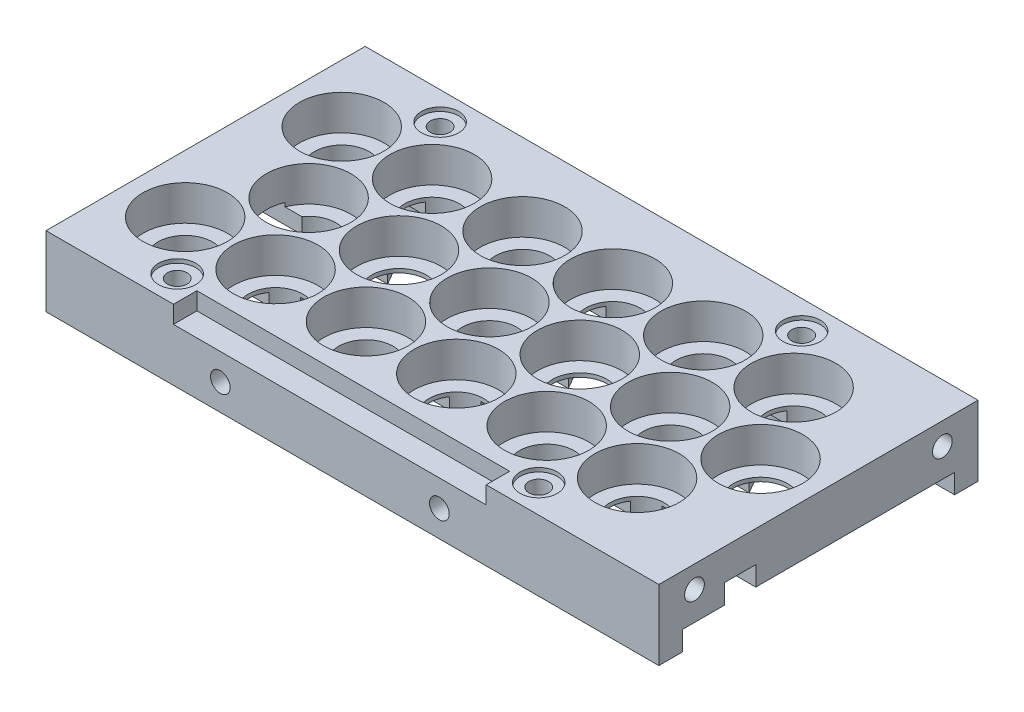
SolidWorks part; units mm, degrees
ref_plane "Front Plane" through (0, 0, 0) normal (0, 0, 1) x (1, 0, 0)
ref_plane "Top Plane" through (0, 0, 0) normal (0, 1, 0) x (1, 0, 0)
ref_plane "Right Plane" through (0, 0, 0) normal (1, 0, 0) x (0, 0, -1)
sketch "Sketch1" plane through (0, 0, 0) normal (0, 1, 0) x (1, 0, 0)
  line L0 (0, 0) -> (11.575, -20.0485) construction
  line L1 (11.575, -20.0485) -> (0, -40.097) construction
  line L2 (0, 0) -> (11.575, 0) construction
  line L3 (11.575, 0) -> (11.575, -20.0485) construction
  line L4 (11.575, -20.0485) -> (11.575, -40.097) construction
  line L5 (11.575, -40.097) -> (0, -40.097) construction
  line L6 (0, 0) -> (23.15, 0) construction
  line L7 (0, 0) -> (23.15, 0) construction
  line L8 (-14.825, -60.922) -> (142.15, -60.922)
  line L9 (-14.825, -60.922) -> (-14.825, 20.825)
  line L10 (-14.825, 20.825) -> (142.15, 20.825)
  line L11 (142.15, -60.922) -> (142.15, 20.825)
  circle A0 centre (0, 0) radius 10.825
  circle A1 centre (11.575, -20.0485) radius 10.825
  circle A2 centre (0, -40.097) radius 10.825
  circle A3 centre (23.15, 0) radius 10.825
  circle A4 centre (34.725, -20.0485) radius 10.825
  circle A5 centre (23.15, -40.097) radius 10.825
  circle A6 centre (46.3, 0) radius 10.825
  circle A7 centre (57.875, -20.0485) radius 10.825
  circle A8 centre (46.3, -40.097) radius 10.825
  circle A9 centre (69.45, 0) radius 10.825
  circle A10 centre (81.025, -20.0485) radius 10.825
  circle A11 centre (69.45, -40.097) radius 10.825
  circle A12 centre (92.6, 0) radius 10.825
  circle A13 centre (104.175, -20.0485) radius 10.825
  circle A14 centre (92.6, -40.097) radius 10.825
  circle A15 centre (115.75, 0) radius 10.825
  circle A16 centre (127.325, -20.0485) radius 10.825
  circle A17 centre (115.75, -40.097) radius 10.825
  circle A18 centre (0, 0) radius 7
  circle A19 centre (11.575, -20.0485) radius 7
  circle A20 centre (0, -40.097) radius 7
  circle A21 centre (23.15, 0) radius 7
  circle A22 centre (34.725, -20.0485) radius 7
  circle A23 centre (23.15, -40.097) radius 7
  circle A24 centre (46.3, 0) radius 7
  circle A25 centre (57.875, -20.0485) radius 7
  circle A26 centre (46.3, -40.097) radius 7
  circle A27 centre (69.45, 0) radius 7
  circle A28 centre (81.025, -20.0485) radius 7
  circle A29 centre (69.45, -40.097) radius 7
  circle A30 centre (92.6, 0) radius 7
  circle A31 centre (104.175, -20.0485) radius 7
  circle A32 centre (92.6, -40.097) radius 7
  circle A33 centre (115.75, 0) radius 7
  circle A34 centre (127.325, -20.0485) radius 7
  circle A35 centre (115.75, -40.097) radius 7
  dimension "D3" = 21.65
  dimension "D11" = 14
  dimension "D1" = 60
  dimension "D2" = 60
  dimension "D4" = 1.5
  dimension "D6" = 23.15
  dimension "D7" = 4
  dimension "D8" = 4
  dimension "D9" = 10
  dimension "D10" = 10
  dimension "D13" = 23.15
  dimension "D5" = 6
  dimension "D12" = 6
extrude "Boss-Extrude2" add sketch "Sketch1" along normal blind 11 and the other way blind 2 contours L8 L11 L10 L9 A17 A16 A15 A14 A13 A12 A11 A10 A9 A8 A7 A6 A5 A4 A3 A2 A1 A0 region at (-13.0551, 0, 20.0485)
extrude "Boss-Extrude3" add sketch "Sketch1<3>" along normal blind 2 and the other way blind 2 contours A0 A18 | A3 A21 | A6 A24 | A9 A27 | A12 A30 | A15 A33 | A1 A19 | A4 A22 | A7 A25 | A10 A28 | A13 A31 | A16 A34 | A17 A35 | A14 A32 | A11 A29 | A8 A26 | A5 A23 | A2 A20 region at (-10.5188, 0, 0) region at (1.0562, 0, 20.0485) region at (-10.5188, 0, 40.097) region at (12.6312, 0, 0) region at (24.2062, 0, 20.0485) region at (12.6312, 0, 40.097) region at (35.7812, 0, 0) region at (47.3562, 0, 20.0485) region at (35.7812, 0, 40.097) region at (58.9312, 0, 0) region at (70.5062, 0, 20.0485) region at (58.9312, 0, 40.097) region at (82.0812, 0, 0) region at (93.6562, 0, 20.0485) region at (82.0812, 0, 40.097) region at (105.2312, 0, 0) region at (116.8062, 0, 20.0485) region at (105.2312, 0, 40.097)
sketch "Sketch1<3>" plane through (0, 0, 0) normal (0, 1, 0) x (1, 0, 0) same geometry as "Sketch1"
sketch "Sketch9" plane through (0, 11, 0) normal (0, 1, 0) x (1, 0, 0)
  line L0 (11.575, -60.922) -> (11.575, 20.825)
  line L1 (-14.825, 20.825) -> (142.15, 20.825) construction
  line L2 (104.175, 20.825) -> (104.175, -60.922)
  line L3 (-14.825, -60.922) -> (142.15, -60.922) construction
  circle A0 centre (11.575, 13.625) radius 2.525
  circle A1 centre (11.575, -53.722) radius 2.525
  circle A2 centre (104.175, -53.722) radius 2.525
  circle A3 centre (104.175, 13.625) radius 2.525
  point P0 (11.575, 13.625)
  point P7 (11.575, -20.0485)
  point P15 (104.175, -20.0485)
  point P20 (104.175, 13.625)
  point P21 (104.175, -53.722)
  point P22 (11.575, -53.722)
  dimension "D5" = 5.05
  dimension "D1" = 7.2
  dimension "D4" = 7.2
extrude "Cut-Extrude3" cut sketch "Sketch9" against normal up to next contours A2 | A1 | A0 | A3
sketch "Sketch10" plane through (0, 11, 0) normal (0, 1, 0) x (1, 0, 0)
  circle A0 centre (11.575, 13.625) radius 4.7625
  circle A1 centre (104.175, 13.625) radius 4.7625
  circle A2 centre (104.175, -53.722) radius 4.7625
  circle A3 centre (11.575, -53.722) radius 4.7625
  dimension "D1" = 9.525
extrude "Cut-Extrude4" cut sketch "Sketch10" against normal blind 1
sketch "Sketch13" plane through (0, -2, 0) normal (0, -1, 0) x (1, 0, 0)
  line L0 (142.15, 60.922) -> (142.15, -20.825) construction
  line L5 (3.575, 53.722) -> (3.575, 60.922)
  line L8 (-14.825, 60.922) -> (142.15, 60.922) construction
  line L9 (3.575, 60.922) -> (19.575, 60.922)
  line L10 (19.575, 60.922) -> (19.575, 53.722)
  line L12 (57.875, 20.0485) -> (57.875, -20.825) construction
  line L13 (-14.825, -20.825) -> (142.15, -20.825) construction
  line L14 (11.575, 20.0485) -> (127.325, 20.0485) construction
  line L16 (96.175, 60.922) -> (96.175, 53.722)
  line L17 (112.175, 60.922) -> (96.175, 60.922)
  line L18 (112.175, 53.722) -> (112.175, 60.922)
  line L19 (-14.825, 60.922) -> (142.15, 60.922)
  line L20 (-14.825, 60.922) -> (-14.825, 54.922)
  line L21 (-14.825, 54.922) -> (142.15, 54.922)
  line L22 (142.15, 60.922) -> (142.15, 54.922)
  line L23 (142.15, -20.825) -> (142.15, -14.825)
  line L24 (-14.825, -14.825) -> (142.15, -14.825)
  line L25 (-14.825, -20.825) -> (-14.825, -14.825)
  line L26 (-14.825, -20.825) -> (142.15, -20.825)
  line L27 (112.175, -13.625) -> (112.175, -20.825)
  line L28 (112.175, -20.825) -> (96.175, -20.825)
  line L29 (96.175, -20.825) -> (96.175, -13.625)
  line L32 (19.575, -20.825) -> (19.575, -13.625)
  line L33 (3.575, -20.825) -> (19.575, -20.825)
  line L34 (3.575, -13.625) -> (3.575, -20.825)
  circle A4 centre (11.575, 53.722) radius 6.5
  circle A5 centre (11.575, 53.722) radius 8
  circle A6 centre (104.175, 53.722) radius 8
  circle A7 centre (104.175, 53.722) radius 6.5
  circle A8 centre (104.175, -13.625) radius 6.5
  circle A9 centre (104.175, -13.625) radius 8
  circle A10 centre (11.575, -13.625) radius 8
  circle A11 centre (11.575, -13.625) radius 6.5
  line M15 (142.15, 60.922) -> (-14.825, 60.922)
  line M16 (-14.825, 60.922) -> (-14.825, -20.825)
  line M17 (-14.825, -20.825) -> (142.15, -20.825)
  line M18 (142.15, -20.825) -> (142.15, 60.922)
  dimension "D1" = 13
  dimension "D2" = 16
  dimension "D3" = 6
extrude "Boss-Extrude7" add sketch "Sketch13" along normal blind 5 contours L21 L5 M16 M15 | A5 L5 L21 M15 | A5 L21 L10 M15 | L10 L21 L16 M15 | L21 A5 L19 A4 | A5 L21 A4 | L21 A6 L16 M15 | L21 A7 A6 L19 | L21 A7 A6 | A6 L21 L18 M15 | L18 L21 M18 M15 | A9 L24 L29 L26 | L28 A9 L24 A8 | A9 L26 L27 L24 | L24 L27 L26 M18 | L32 L26 L29 L24 | L24 A9 A8 | L34 L24 M16 M17 | L26 A10 L24 L34 | L24 A11 A10 | L24 A11 A10 L33 | L24 A10 L26 L32 region at (3.7817, -2, 54.3098) region at (-5.625, -2, 57.922) region at (4.8282, -2, 59.2567) region at (5.2714, -2, 58.3681) region at (18.3218, -2, 59.2567) region at (57.875, -2, 57.922) region at (-5.625, -2, -17.825) region at (97.4282, -2, 59.2567) region at (4.8282, -2, -19.1597) region at (96.3817, -2, 54.3098) region at (97.8714, -2, 58.3681) region at (3.7817, -2, -14.2128) region at (4.4261, -2, -14.9942) region at (110.9218, -2, 59.2567) region at (127.1625, -2, 57.922) region at (18.3218, -2, -19.1597) region at (57.875, -2, -17.825) region at (97.4282, -2, -19.1597) region at (127.1625, -2, -17.825) region at (96.3817, -2, -14.2128) region at (97.0261, -2, -14.9942) region at (110.9218, -2, -19.1597)
sketch "Sketch2" plane through (0, -2, 0) normal (0, -1, 0) x (1, 0, 0)
  line L0 (0, 40.097) -> (11.575, 20.0485) construction
  line L1 (3.4641, 42.097) -> (15.0391, 22.0485)
  line L2 (-3.4641, 38.097) -> (8.1109, 18.0485)
  line L3 (11.575, 20.0485) -> (0, 0) construction
  line L4 (15.0391, 18.0485) -> (3.4641, -2)
  line L5 (8.1109, 22.0485) -> (-3.4641, 2)
  line L6 (19.6859, 38.097) -> (31.2609, 18.0485)
  line L7 (26.6141, 42.097) -> (38.1891, 22.0485)
  line L8 (31.2609, 22.0485) -> (19.6859, 2)
  line L9 (38.1891, 18.0485) -> (26.6141, -2)
  line L10 (23.15, 40.097) -> (34.725, 20.0485) construction
  line L11 (34.725, 20.0485) -> (23.15, 0) construction
  line L12 (42.8359, 38.097) -> (54.4109, 18.0485)
  line L13 (49.7641, 42.097) -> (61.3391, 22.0485)
  line L14 (54.4109, 22.0485) -> (42.8359, 2)
  line L15 (61.3391, 18.0485) -> (49.7641, -2)
  line L16 (46.3, 40.097) -> (57.875, 20.0485) construction
  line L17 (57.875, 20.0485) -> (46.3, 0) construction
  line L18 (65.9859, 38.097) -> (77.5609, 18.0485)
  line L19 (72.9141, 42.097) -> (84.4891, 22.0485)
  line L20 (77.5609, 22.0485) -> (65.9859, 2)
  line L21 (84.4891, 18.0485) -> (72.9141, -2)
  line L22 (69.45, 40.097) -> (81.025, 20.0485) construction
  line L23 (81.025, 20.0485) -> (69.45, 0) construction
  line L24 (89.1359, 38.097) -> (100.7109, 18.0485)
  line L25 (96.0641, 42.097) -> (107.6391, 22.0485)
  line L26 (100.7109, 22.0485) -> (89.1359, 2)
  line L27 (107.6391, 18.0485) -> (96.0641, -2)
  line L28 (92.6, 40.097) -> (104.175, 20.0485) construction
  line L29 (104.175, 20.0485) -> (92.6, 0) construction
  line L30 (112.2859, 38.097) -> (123.8609, 18.0485)
  line L31 (119.2141, 42.097) -> (130.7891, 22.0485)
  line L32 (123.8609, 22.0485) -> (112.2859, 2)
  line L33 (130.7891, 18.0485) -> (119.2141, -2)
  line L34 (115.75, 40.097) -> (127.325, 20.0485) construction
  line L35 (127.325, 20.0485) -> (115.75, 0) construction
  line L36 (-3.4641, 38.097) -> (19.6859, 38.097) construction
  line L37 (0, 40.097) -> (115.75, 40.097) construction
  line L38 (0, 44.097) -> (115.75, 44.097)
  line L39 (0, 36.097) -> (115.75, 36.097)
  line L40 (11.575, 20.0485) -> (127.325, 20.0485) construction
  line L41 (11.575, 24.0485) -> (127.325, 24.0485)
  line L42 (11.575, 16.0485) -> (127.325, 16.0485)
  line L43 (0, 0) -> (115.75, 0) construction
  line L44 (0, 4) -> (115.75, 4)
  line L45 (0, -4) -> (115.75, -4)
  arc A0 (3.4641, 42.097) -> (-3.4641, 38.097) centre (0, 40.097) ccw
  arc A1 (8.1109, 18.0485) -> (15.0391, 22.0485) centre (11.575, 20.0485) ccw
  arc A2 (15.0391, 18.0485) -> (8.1109, 22.0485) centre (11.575, 20.0485) ccw
  arc A3 (-3.4641, 2) -> (3.4641, -2) centre (0, 0) ccw
  arc A4 (26.6141, 42.097) -> (19.6859, 38.097) centre (23.15, 40.097) ccw
  arc A5 (31.2609, 18.0485) -> (38.1891, 22.0485) centre (34.725, 20.0485) ccw
  arc A6 (38.1891, 18.0485) -> (31.2609, 22.0485) centre (34.725, 20.0485) ccw
  arc A7 (19.6859, 2) -> (26.6141, -2) centre (23.15, 0) ccw
  arc A8 (49.7641, 42.097) -> (42.8359, 38.097) centre (46.3, 40.097) ccw
  arc A9 (54.4109, 18.0485) -> (61.3391, 22.0485) centre (57.875, 20.0485) ccw
  arc A10 (61.3391, 18.0485) -> (54.4109, 22.0485) centre (57.875, 20.0485) ccw
  arc A11 (42.8359, 2) -> (49.7641, -2) centre (46.3, 0) ccw
  arc A12 (72.9141, 42.097) -> (65.9859, 38.097) centre (69.45, 40.097) ccw
  arc A13 (77.5609, 18.0485) -> (84.4891, 22.0485) centre (81.025, 20.0485) ccw
  arc A14 (84.4891, 18.0485) -> (77.5609, 22.0485) centre (81.025, 20.0485) ccw
  arc A15 (65.9859, 2) -> (72.9141, -2) centre (69.45, 0) ccw
  arc A16 (96.0641, 42.097) -> (89.1359, 38.097) centre (92.6, 40.097) ccw
  arc A17 (100.7109, 18.0485) -> (107.6391, 22.0485) centre (104.175, 20.0485) ccw
  arc A18 (107.6391, 18.0485) -> (100.7109, 22.0485) centre (104.175, 20.0485) ccw
  arc A19 (89.1359, 2) -> (96.0641, -2) centre (92.6, 0) ccw
  arc A20 (119.2141, 42.097) -> (112.2859, 38.097) centre (115.75, 40.097) ccw
  arc A21 (123.8609, 18.0485) -> (130.7891, 22.0485) centre (127.325, 20.0485) ccw
  arc A22 (130.7891, 18.0485) -> (123.8609, 22.0485) centre (127.325, 20.0485) ccw
  arc A23 (112.2859, 2) -> (119.2141, -2) centre (115.75, 0) ccw
  arc A24 (0, 44.097) -> (0, 36.097) centre (0, 40.097) ccw
  arc A25 (115.75, 36.097) -> (115.75, 44.097) centre (115.75, 40.097) ccw
  arc A26 (11.575, 24.0485) -> (11.575, 16.0485) centre (11.575, 20.0485) ccw
  arc A27 (127.325, 16.0485) -> (127.325, 24.0485) centre (127.325, 20.0485) ccw
  arc A28 (0, 4) -> (0, -4) centre (0, 0) ccw
  arc A29 (115.75, -4) -> (115.75, 4) centre (115.75, 0) ccw
  point P3 (5.7875, 30.0727)
  point P8 (5.7875, 10.0242)
  point P18 (28.9375, 30.0727)
  point P25 (28.9375, 10.0242)
  point P34 (52.0875, 30.0727)
  point P39 (52.0875, 10.0242)
  point P48 (75.2375, 30.0727)
  point P53 (75.2375, 10.0242)
  point P62 (98.3875, 30.0727)
  point P67 (98.3875, 10.0242)
  point P76 (121.5375, 30.0727)
  point P81 (121.5375, 10.0242)
  point P91 (57.875, 40.097)
  point P96 (69.45, 20.0485)
  point P103 (57.875, 0)
  dimension "D1" = 8
  dimension "D3" = 23.15
  dimension "D4" = 8
  dimension "D5" = 8
  dimension "D6" = 8
extrude "Cut-Extrude1" cut sketch "Sketch2" against normal blind 3 contours L1 L39 L38 | L42 L8 L6 L41 | L13 L39 L38 | L18 L41 L19 L39 | L25 L39 L38 | L42 L32 L30 L41 | L42 L20 L18 L41 | L45 L44 L4 | L45 L44 L15 | L45 L44 L27 | L44 L21 L42 L20 | L39 L13 | L39 L25 | L39 L19 | L41 L6 | L44 L4 | L44 L15 | L44 L21 | L44 L27 | L41 L30 | L32 L42 | L41 L18 | L20 L42 | L44 L9 L42 L8 | L8 L42 | L39 L7 | L39 L1 | A23 L32 L44 L45 | L30 L41 L31 | L42 L32 L33 | L6 L41 L7 L39 | A7 L9 L44 L8 region at (12.1489, -2, 40.3471) region at (0.784, -2, 39.6443) region at (21.9471, -2, 20.0485) region at (28.9375, -2, 30.0727) region at (23.8945, -2, 39.601) region at (30.3235, -2, 22.793) region at (58.4489, -2, 40.3471) region at (47.0445, -2, 39.601) region at (30.3235, -2, 17.304) region at (70.1945, -2, 39.601) region at (0.784, -2, 0.4527) region at (28.9375, -2, 10.0242) region at (104.7489, -2, 40.3471) region at (93.3445, -2, 39.601) region at (12.1489, -2, -0.2501) region at (23.8945, -2, 0.496) region at (68.2471, -2, 20.0485) region at (75.2375, -2, 30.0727) region at (76.6235, -2, 22.793) region at (121.4671, -2, 30.6948) region at (58.4489, -2, -0.2501) region at (47.0445, -2, 0.496) region at (76.6235, -2, 17.304) region at (114.5471, -2, 20.0485) region at (70.1945, -2, 0.496) region at (75.2375, -2, 10.0242) region at (121.4671, -2, 9.4022) region at (122.9235, -2, 22.793) region at (104.7489, -2, -0.2501) region at (93.3445, -2, 0.496) region at (122.9235, -2, 17.304)
sketch "Sketch19" plane through (0, 0, 60.922) normal (0, 0, 1) x (1, 0, 0)
  line L0 (11.575, 11) -> (104.175, 11)
  line L1 (-14.825, 11) -> (142.15, 11) construction
  line L2 (97.925, 11) -> (17.825, 11)
  line L3 (17.825, 11) -> (97.925, 11)
  line L4 (17.825, 11) -> (17.825, 6.525)
  line L5 (97.925, 11) -> (97.925, 6.525)
  line L6 (17.825, 6.525) -> (97.925, 6.525)
  point P5 (57.875, 11)
  point P9 (57.875, 11)
  dimension "D1" = 92.6
  dimension "D2" = 26.4
  dimension "D3" = 80.1
  dimension "D4" = 4.475
extrude "Cut-Extrude6" cut sketch "Sketch19" against normal blind 6 contours L4 L6 L5 L0 region at (57.875, 8.7625, 60.922)
sketch "Sketch20" plane through (0, 0, 60.922) normal (0, 0, 1) x (1, 0, 0)
  line L0 (29.825, 6.525) -> (85.925, 6.525)
  line L1 (29.825, 6.525) -> (29.825, -0.2375)
  line L2 (85.925, 6.525) -> (85.925, -0.2375)
  line L3 (29.825, -0.2375) -> (85.925, -0.2375)
  line L4 (29.825, 6.525) -> (17.825, 6.525) construction
  line L5 (85.925, 6.525) -> (97.925, 6.525) construction
  line L6 (57.875, 6.525) -> (57.875, -7)
  line L9 (142.15, -7) -> (-14.825, -7) construction
  circle A0 centre (29.825, -0.2375) radius 2.525
  circle A1 centre (85.925, -0.2375) radius 2.525
  point P9 (57.875, -0.2375)
  dimension "D2" = 5.05
  dimension "D1" = 12
extrude "Cut-Extrude7" cut sketch "Sketch20" against normal blind 3.8862 contours L1 A0 L3 | L3 A0 L1 | L3 A1 L2 | L2 A1 L3 region at (30.8966, 0.8341, 60.922) region at (29.4678, -0.5947, 60.922) region at (86.2822, -0.5947, 60.922) region at (84.8534, 0.8341, 60.922)
sketch "Sketch22" plane through (142.15, 0, 0) normal (1, 0, 0) x (0, 0, -1)
  circle A0 centre (-51.7985, 5.325) radius 2.525
  circle A1 centre (11.7015, 5.325) radius 2.525
  circle A2 centre (-51.7985, 5.325) radius 2.525 construction
  circle A3 centre (11.7015, 5.325) radius 2.525 construction
  dimension "D1" = 5.05
extrude "Cut-Extrude8" cut sketch "Sketch22" against normal blind 3.81 contours A0 | A0 | A1 | A1 region at (142.15, 5.325, 51.7985) region at (142.15, 5.325, -11.7015)
sketch "Sketch26" plane through (0, -2, 0) normal (0, -1, 0) x (1, 0, 0)
  line L0 (57.875, -14.825) -> (57.875, -4) construction
  line L1 (132.15, -9.4125) -> (57.875, -9.4125) construction
  line L2 (57.875, -9.4125) -> (-10.825, -9.4125) construction
  line L3 (11.575, 20.0485) -> (82.7573, 20.0485)
  line L4 (57.875, 49.5095) -> (-10.825, 49.5095) construction
  line L5 (132.15, 49.5095) -> (57.875, 49.5095) construction
  line L6 (57.875, 54.922) -> (57.875, 44.097) construction
  line L7 (19.4845, 54.922) -> (96.2655, 54.922) construction
  line L8 (52.0446, 44.097) -> (63.7054, 44.097) construction
  line L9 (-14.825, 54.922) -> (-14.825, -14.825) construction
  line L10 (142.15, 54.922) -> (142.15, -14.825) construction
  circle A0 centre (132.15, -9.4125) radius 1.9431
  circle A1 centre (57.875, -9.4125) radius 1.9431
  circle A2 centre (-10.825, -9.4125) radius 1.9431
  circle A3 centre (-10.825, 49.5095) radius 1.9431
  circle A4 centre (57.875, 49.5095) radius 1.9431
  circle A5 centre (132.15, 49.5095) radius 1.9431
  dimension "D1" = 3.8862
  dimension "D2" = 4
  dimension "D3" = 10
extrude "Cut-Extrude9" cut sketch "Sketch26" against normal blind 5 contours A3 | A4 | A5 | A2 | A1 | A0
sketch "Sketch27" plane through (0, -2, 0) normal (0, -1, 0) x (1, 0, 0)
  line L0 (11.575, 20.0485) -> (-14.825, 20.0485) construction
  line L1 (-14.825, 54.922) -> (-14.825, -14.825) construction
  line L2 (11.575, 16.0485) -> (-14.825, 16.0485)
  line L3 (11.575, 24.0485) -> (-14.825, 24.0485)
  line L4 (115.75, 40.097) -> (142.15, 40.097) construction
  line L5 (142.15, 54.922) -> (142.15, -14.825) construction
  line L6 (115.75, 44.097) -> (142.15, 44.097)
  line L7 (115.75, 36.097) -> (142.15, 36.097)
  arc A0 (11.575, 16.0485) -> (11.575, 24.0485) centre (11.575, 20.0485) ccw
  arc A1 (-14.825, 24.0485) -> (-14.825, 16.0485) centre (-14.825, 20.0485) ccw
  arc A2 (115.75, 44.097) -> (115.75, 36.097) centre (115.75, 40.097) ccw
  arc A3 (142.15, 36.097) -> (142.15, 44.097) centre (142.15, 40.097) ccw
  point P5 (-1.625, 20.0485)
  point P15 (128.95, 40.097)
  dimension "D1" = 8
  dimension "D2" = 8
extrude "Cut-Extrude10" cut sketch "Sketch27" against normal blind 5
sketch "Sketch28" plane through (0, 3, 0) normal (0, -1, 0) x (1, 0, 0)
  line L0 (0.75, 20.0485) -> (-14.825, 20.0485) construction
  line L1 (-14.825, 24.0485) -> (-14.825, 16.0485) construction
  line L2 (142.15, 40.097) -> (126.575, 40.097) construction
  line L3 (142.15, 44.097) -> (142.15, 36.097) construction
  circle A0 centre (-10.825, 20.0485) radius 1.9431
  circle A1 centre (-3.25, 20.0485) radius 1.9431
  arc A2 (1.5161, 24.0485) -> (1.5161, 16.0485) centre (11.575, 20.0485) ccw construction
  circle A3 centre (130.575, 40.097) radius 1.9431
  circle A4 centre (138.15, 40.097) radius 1.9431
  arc A5 (125.8089, 36.097) -> (125.8089, 44.097) centre (115.75, 40.097) ccw construction
  point P4 (-11.0817, 20.0485)
  point P5 (-4.3704, 20.0485)
  point P19 (126.575, 40.097)
  point P23 (142.15, 40.097)
  point P26 (131.5431, 40.097)
  dimension "D1" = 3.8862
  dimension "D2" = 4
  dimension "D4" = 3.8862
  dimension "D3" = 4
  dimension "D5" = 4
  dimension "D6" = 4
extrude "Cut-Extrude11" cut sketch "Sketch28" against normal blind 5
equation "\"hole_diameter\"= 21.65"
equation "\"D3@Sketch1\"=\"hole_diameter\""
equation "\"cell_spacing\"= 1.5"
equation "\"D4@Sketch1\"=\"cell_spacing\""
equation "\"D6@Sketch1\"=\"hole_diameter\"+\"cell_spacing\""
equation "\"len_spacing\"= 4"
equation "\"D7@Sketch1\"=\"len_spacing\""
equation "\"D8@Sketch1\"=\"len_spacing\""
equation "\"wid_spacing\"= 10"
equation "\"D9@Sketch1\"=\"wid_spacing\""
equation "\"D10@Sketch1\"=\"wid_spacing\""
equation "\"nipple\"= 14"
equation "\"D11@Sketch1\"=\"nipple\""
equation "\"D13@Sketch1\"=\"hole_diameter\"+\"cell_spacing\""
equation "\"channel\"= 8"
equation "\"D1@Sketch2\"=\"channel\""
equation "\"D3@Sketch2\"=\"hole_diameter\"+\"cell_spacing\""
equation "\"D4@Sketch2\"=\"channel\""
equation "\"D5@Sketch2\"=\"channel\""
equation "\"D6@Sketch2\"=\"channel\""
equation "\"lip\"= 6"
equation "\"lip_height\"= 1"
equation "\"outer_fillet\"=6"
equation "\"insert_placement\"= 7.2"
equation "\"D4@Sketch9\"=\"insert_placement\""
equation "\"D1@Sketch9\"=\"insert_placement\""
equation "\"heat_insert_diameter\"= 5.05"
equation "\"D5@Sketch9\"=\"heat_insert_diameter\""
equation "\"heat_insert_lip_diameter\"=9.525"
equation "\"D1@Sketch10\"=\"heat_insert_lip_diameter\""
equation "\"bolt_head_diameter\"=13"
equation "\"D1@Sketch13\"=\"bolt_head_diameter\""
equation "\"D2@Sketch13\"=\"bolt_head_diameter\"+3"
equation "\"D3@Sketch13\"=\"lip\""
equation "\"small_heat_insert\"= .153in"
equation "\"bdm_cut_depth\"=6"
equation "\"D1@Cut-Extrude6\"=\"bdm_cut_depth\""
equation "\"D1@Cut-Extrude7\"=\"small_heat_insert\""
equation "\"D2@Sketch20\"=\"heat_insert_diameter\""
equation "\"heat_insert_depth\"= .15in"
equation "\"D1@Cut-Extrude8\"=\"heat_insert_depth\""
equation "\"D1@Sketch26\"=\"small_heat_insert\""
equation "\"D1@Sketch27\"=\"channel\""
equation "\"D2@Sketch27\"=\"channel\""
equation "\"D1@Sketch28\"=\"small_heat_insert\""
equation "\"D4@Sketch28\"=\"small_heat_insert\""
equation "\"D1@Sketch22\"=\"heat_insert_diameter\""
equation "\"heat_insert_space\"=6"
equation "\"heat_insert\"=5.5"
